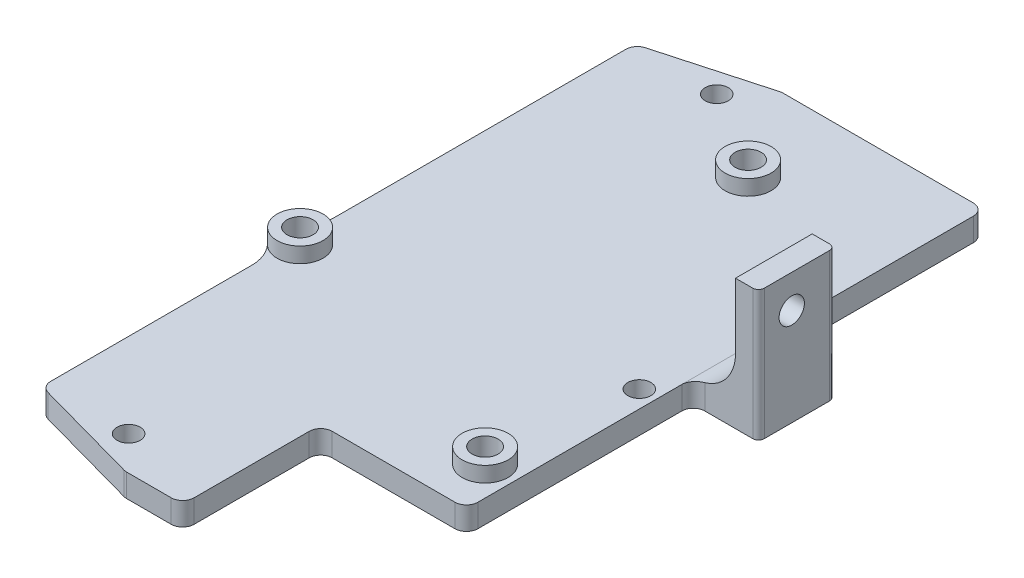
SolidWorks part; units mm, degrees
ref_plane "Front Plane" through (0, 0, 0) normal (0, 0, 1) x (1, 0, 0)
ref_plane "Top Plane" through (0, 0, 0) normal (0, 1, 0) x (1, 0, 0)
ref_plane "Right Plane" through (0, 0, 0) normal (1, 0, 0) x (0, 0, -1)
sketch "Sketch1" plane through (0, 0, 0) normal (0, 1, 0) x (1, 0, 0)
  line L0 (0, 0) -> (7, 0)
  line L1 (0, 3.75) -> (7, 3.75)
  line L2 (0, -3.75) -> (7, -3.75)
  circle A0 centre (0, 0) radius 3.75
  circle A1 centre (7, 0) radius 3.75
  dimension "D1" = 7.5
  dimension "D2" = 7
extrude "Boss-Extrude2" add sketch "Sketch1" along normal blind 30
sketch "Sketch4" plane through (0, 30, 0) normal (0, 1, 0) x (1, 0, 0)
  line L2 (7, 3.75) -> (0, 3.75)
  line L3 (0, -3.75) -> (7, -3.75)
  line L4 (7, 3.75) -> (0, 3.75)
  line L5 (0, -3.75) -> (7, -3.75)
  circle A0 centre (7, 0) radius 3.75
  arc A3 (0, 3.75) -> (0, -3.75) centre (0, 0) ccw
  arc A4 (7, -3.75) -> (7, 3.75) centre (7, 0) ccw
  arc A5 (0, 3.75) -> (0, -3.75) centre (0, 0) ccw
  arc A6 (7, -3.75) -> (7, 3.75) centre (7, 0) ccw
  line M6 (7, 3.75) -> (0, 3.75)
  arc M7 (0, 3.75) -> (0, -3.75) centre (0, 0) ccw
  line M8 (0, -3.75) -> (7, -3.75)
  dimension "D1" = 0
extrude "Cut-Extrude3" cut sketch "Sketch4" against normal blind 13 contours A0 M6 M7 M8
sketch "Sketch5" plane through (0, 0, 0) normal (0, -1, 0) x (1, 0, 0)
  line L0 (10.75, 0) -> (10.75, -52.5)
  line L1 (10.75, -52.5) -> (-39.25, -38.6338)
  line L2 (-39.25, -38.6338) -> (-39.25, -35)
  line L3 (-39.25, -35) -> (-9.25, -35)
  line L4 (-9.25, -35) -> (-9.25, 35)
  line L5 (-9.25, 35) -> (-39.25, 35)
  line L6 (-39.25, 35) -> (-39.25, 38.6338)
  line L7 (-39.25, 38.6338) -> (10.75, 52.5)
  line L8 (10.75, 52.5) -> (10.75, 0)
  arc A0 (7, -3.75) -> (7, 3.75) centre (7, 0) ccw construction
  dimension "D1" = 50
  dimension "D2" = 105
  dimension "D3" = 74.5
  dimension "D4" = 70
  dimension "D5" = 30
extrude "Boss-Extrude3" add sketch "Sketch5" against normal blind 3
sketch "Sketch6" plane through (0, 3, 0) normal (0, 1, 0) x (1, 0, 0)
  line L46 (-24.25, -42.7936) -> (-24.25, 42.7936)
  line L54 (10.75, 52.5) -> (-39.25, 38.6338)
  line L55 (10.75, -52.5) -> (10.75, 52.5)
  line L56 (-39.25, -38.6338) -> (10.75, -52.5)
  line L57 (-39.25, -35) -> (-39.25, -38.6338)
  line L58 (-9.25, -35) -> (-39.25, -35)
  line L59 (-9.25, 35) -> (-9.25, -35)
  line L60 (-39.25, 35) -> (-9.25, 35)
  line L61 (-39.25, 38.6338) -> (-39.25, 35)
  line L62 (10.75, 52.5) -> (-39.25, 38.6338)
  line L63 (10.75, -52.5) -> (10.75, 52.5)
  line L64 (-39.25, -38.6338) -> (10.75, -52.5)
  line L65 (-39.25, -35) -> (-39.25, -38.6338)
  line L66 (-9.25, -35) -> (-39.25, -35)
  line L67 (-9.25, 35) -> (-9.25, -35)
  line L68 (-39.25, 35) -> (-9.25, 35)
  line L69 (-39.25, 38.6338) -> (-39.25, 35)
  line M12 (10.75, 52.5) -> (-39.25, 38.6338)
  line M13 (-39.25, 38.6338) -> (-39.25, 35)
  line M14 (-39.25, 35) -> (-9.25, 35)
  line M16 (-9.25, -35) -> (-39.25, -35)
  line M17 (-39.25, -35) -> (-39.25, -38.6338)
  line M18 (-39.25, -38.6338) -> (10.75, -52.5)
  dimension "D2" = 15
  dimension "D1" = 0
extrude "Boss-Extrude4" add sketch "Sketch6" along normal blind 14 contours L46 M18 M16 M17 | L46 M14 M12 M13
sketch "Sketch7" plane through (0, 17, 0) normal (0, 1, 0) x (1, 0, 0)
  line L0 (-39.25, 38.6338) -> (-39.25, -38.6338)
  line L1 (-39.25, -38.6338) -> (-24.25, -42.7936)
  line L2 (-24.25, -42.7936) -> (2.25, -42.7936)
  line L3 (2.25, -42.7936) -> (2.25, 42.7936)
  line L4 (2.25, 42.7936) -> (-24.25, 42.7936)
  line L5 (-24.25, 42.7936) -> (-39.25, 38.6338)
  dimension "D1" = 41.5
extrude "Boss-Extrude5" add sketch "Sketch7" along normal blind 3
sketch "Sketch8" plane through (0, 20, 0) normal (0, 1, 0) x (1, 0, 0)
  line L0 (-28.25, 38.3422) -> (-28.25, 35)
  line L3 (-24.25, -42.7936) -> (-24.25, 42.7936)
  line L4 (-28.25, 38.3422) -> (-28.25, 41.6843)
  line L5 (-28.25, -41.6843) -> (-28.25, -38.3422)
  line L6 (-28.25, -38.3422) -> (-28.25, -35)
  line L11 (10.75, 52.5) -> (-39.25, 38.6338)
  line L12 (10.75, -52.5) -> (10.75, 52.5)
  line L13 (-39.25, -38.6338) -> (10.75, -52.5)
  line L14 (-39.25, -35) -> (-39.25, -38.6338)
  line L15 (-9.25, -35) -> (-39.25, -35)
  line L16 (-9.25, 35) -> (-9.25, -35)
  line L17 (-39.25, 35) -> (-9.25, 35)
  line L18 (-39.25, 38.6338) -> (-39.25, 35)
  line L19 (10.75, 52.5) -> (-39.25, 38.6338)
  line L20 (10.75, -52.5) -> (10.75, 52.5)
  line L21 (-39.25, -38.6338) -> (10.75, -52.5)
  line L22 (-39.25, -35) -> (-39.25, -38.6338)
  line L23 (-9.25, -35) -> (-39.25, -35)
  line L24 (-9.25, 35) -> (-9.25, -35)
  line L25 (-39.25, 35) -> (-9.25, 35)
  line L26 (-39.25, 38.6338) -> (-39.25, 35)
  circle A0 centre (-28.25, -38.3422) radius 1.5
  circle A1 centre (-28.25, 38.3422) radius 1.5
  dimension "D1" = 3
  dimension "D3" = 4
  dimension "D2" = 0
extrude "Cut-Extrude4" cut sketch "Sketch8" against normal through all contours A1 | A0
sketch "Sketch3" plane through (0, 0, 0) normal (0, -1, 0) x (1, 0, 0)
  circle A0 centre (0, 0) radius 1.5
  dimension "D1" = 3
extrude "Cut-Extrude2" cut sketch "Sketch3" against normal through all
sketch "Sketch2" plane through (0, 30, 0) normal (0, 1, 0) x (1, 0, 0)
  circle A0 centre (7, 0) radius 1.5
  dimension "D1" = 3
extrude "Cut-Extrude1" cut sketch "Sketch2" against normal blind 30
sketch "Sketch9" plane through (2.25, 0, 0) normal (1, 0, 0) x (0, 0, -1)
  line L0 (3.75, 17) -> (42.7936, 17) construction
  line L1 (4.7936, 34) -> (14.7936, 34)
  line L2 (4.7936, 34) -> (4.7936, 17)
  line L3 (4.7936, 17) -> (14.7936, 17)
  line L4 (14.7936, 34) -> (14.7936, 17)
  line L6 (42.7936, 20) -> (42.7936, 17) construction
  dimension "D1" = 28
  dimension "D2" = 10
  dimension "D3" = 17
extrude "Boss-Extrude6" add sketch "Sketch9" along normal blind 8.5
sketch "Sketch11" plane through (10.75, 0, 0) normal (1, 0, 0) x (0, 0, -1)
  line L0 (43.5, 3) -> (43.5, 4)
  line L1 (51.5, 4) -> (51.5, 3)
  line L5 (-52.5, 0) -> (52.5, 0)
  line L6 (52.5, 0) -> (52.5, 3)
  line L7 (52.5, 3) -> (0, 3)
  line L8 (0, 3) -> (-52.5, 3)
  line L9 (-52.5, 3) -> (-52.5, 0)
  line L10 (-52.5, 0) -> (52.5, 0)
  line L11 (52.5, 0) -> (52.5, 3)
  line L12 (52.5, 3) -> (0, 3)
  line L13 (0, 3) -> (-52.5, 3)
  line L14 (-52.5, 3) -> (-52.5, 0)
  arc A0 (43.5, 4) -> (51.5, 4) centre (47.5, 4) cw
  circle A1 centre (47.5, 4) radius 0.875
  line M8 (52.5, 3) -> (0, 3)
  dimension "D4" = 4
  dimension "D5" = 1.75
  dimension "D2" = 1
  dimension "D3" = 5
  dimension "D1" = 0
extrude "Boss-Extrude7" add sketch "Sketch11" against normal blind 10 contours A0 L0 L1 A1 M8
sketch "Sketch12" plane through (0, 3, 0) normal (0, -1, 0) x (1, 0, 0)
  line L3 (7.1441, -51.5) -> (0.75, -49.7268)
  line L4 (0.75, -49.7268) -> (0.75, -51.5)
  line L5 (0.75, -51.5) -> (7.1441, -51.5)
  line L6 (7.1441, -51.5) -> (0.75, -49.7268)
  line L7 (0.75, -49.7268) -> (0.75, -51.5)
  line L8 (0.75, -51.5) -> (7.1441, -51.5)
  dimension "D1" = 0
extrude "Cut-Extrude6" cut sketch "Sketch12" against normal blind 10
sketch "Sketch13" plane through (0, 0, -14.7936) normal (0, 0, -1) x (-1, 0, 0)
  line L0 (-7.75, 34) -> (-7.75, 25.5)
  line L1 (-2.25, 20) -> (1.5008, 20)
  line L5 (-2.25, 17) -> (-2.25, 20)
  line L6 (-2.25, 20) -> (-2.25, 34)
  line L7 (-2.25, 34) -> (-10.75, 34)
  line L8 (-10.75, 34) -> (-10.75, 17)
  line L9 (-10.75, 17) -> (-2.25, 17)
  line L10 (-2.25, 17) -> (-2.25, 20)
  line L11 (-2.25, 20) -> (-2.25, 34)
  line L12 (-2.25, 34) -> (-10.75, 34)
  line L13 (-10.75, 34) -> (-10.75, 17)
  line L14 (-10.75, 17) -> (-2.25, 17)
  arc A0 (-7.75, 25.5) -> (-2.25, 20) centre (-2.25, 25.5) ccw
  line M7 (-2.25, 20) -> (-2.25, 34)
  line M8 (-2.25, 34) -> (-10.75, 34)
  dimension "D2" = 3
  dimension "D1" = 0
extrude "Cut-Extrude7" cut sketch "Sketch13" against normal up to next contours L0 A0 M7 M8
sketch "Sketch14" plane through (10.75, 0, 0) normal (1, 0, 0) x (0, 0, -1)
  line L0 (14.7936, 34) -> (4.7936, 34) construction
  line L1 (4.7936, 34) -> (4.7936, 17) construction
  circle A0 centre (9.1236, 29.69) radius 1.65
  dimension "D3" = 3.3
  dimension "D1" = 4.31
  dimension "D2" = 4.33
extrude "Cut-Extrude8" cut sketch "Sketch14" against normal blind 10 contours A0
sketch "Sketch15" plane through (0, 20, 0) normal (0, 1, 0) x (1, 0, 0)
  line L0 (-39.25, -25.7936) -> (-17.25, -25.7936)
  line L1 (-39.25, 38.6338) -> (-39.25, -38.6338) construction
  line L2 (-17.25, -25.7936) -> (-17.25, -42.7936)
  line L4 (-24.25, -42.7936) -> (2.25, -42.7936) construction
  line L13 (-24.25, 42.7936) -> (-39.25, 38.6338)
  line L14 (-39.25, 38.6338) -> (-39.25, -38.6338)
  line L15 (-39.25, -38.6338) -> (-24.25, -42.7936)
  line L16 (-24.25, -42.7936) -> (2.25, -42.7936)
  line L17 (2.25, -42.7936) -> (2.25, 4.7936)
  line L18 (2.25, 4.7936) -> (2.25, 14.7936)
  line L19 (2.25, 14.7936) -> (2.25, 42.7936)
  line L20 (2.25, 42.7936) -> (-24.25, 42.7936)
  line L21 (-24.25, 42.7936) -> (-39.25, 38.6338)
  line L22 (-39.25, 38.6338) -> (-39.25, -38.6338)
  line L23 (-39.25, -38.6338) -> (-24.25, -42.7936)
  line L24 (-24.25, -42.7936) -> (2.25, -42.7936)
  line L25 (2.25, -42.7936) -> (2.25, 4.7936)
  line L26 (2.25, 4.7936) -> (2.25, 14.7936)
  line L27 (2.25, 14.7936) -> (2.25, 42.7936)
  line L28 (2.25, 42.7936) -> (-24.25, 42.7936)
  circle M12 centre (-28.25, -38.3422) radius 1.5
  line M15 (-39.25, 38.6338) -> (-39.25, -38.6338)
  line M16 (-39.25, -38.6338) -> (-24.25, -42.7936)
  line M17 (-24.25, -42.7936) -> (2.25, -42.7936)
  dimension "D1" = 22
  dimension "D2" = 17
  dimension "D3" = 0
extrude "Boss-Extrude8" add sketch "Sketch15" along normal blind 20 contours L2 L0 M15 M16 M17 M12
sketch "Sketch16" plane through (-17.25, 0, 0) normal (1, 0, 0) x (0, 0, -1)
  line L0 (-25.7936, 40) -> (-25.7936, 20) construction
  line L1 (-42.7936, 40) -> (-25.7936, 40)
  line L2 (-42.7936, 40) -> (-42.7936, 35)
  line L3 (-42.7936, 35) -> (-25.7936, 35)
  line L4 (-25.7936, 40) -> (-25.7936, 35)
  dimension "D1" = 5
extrude "Boss-Extrude9" add sketch "Sketch16" along normal blind 25
sketch "Sketch17" plane through (0, 40, 0) normal (0, 1, 0) x (1, 0, 0)
  line L0 (-0.25, -34.2936) -> (7.75, -34.2936)
  line L1 (7.75, -25.7936) -> (7.75, -42.7936) construction
  circle A0 centre (-0.25, -34.2936) radius 6.25
  dimension "D1" = 12.5
  dimension "D2" = 8
extrude "Cut-Extrude9" cut sketch "Sketch17" against normal up to next contours A0
sketch "Sketch18" plane through (0, 40, 0) normal (0, 1, 0) x (1, 0, 0)
  circle A0 centre (-0.25, -34.2936) radius 11.6726
  circle A1 centre (-0.25, -34.2936) radius 6.25 construction
  circle A2 centre (-0.25, -34.2936) radius 6.25
extrude "Boss-Extrude10" add sketch "Sketch18" against normal up to surface (5 mm away) up to face at (-0.25, 35, 40.5436)
fillet "Fillet1" radius 3 1 edges at (-17.25, 35, 34.2936)
sketch "Sketch19" plane through (0, 20, 0) normal (0, 1, 0) x (1, 0, 0)
  line L1 (2.25, -42.7936) -> (-16.75, -42.7936)
  line L2 (2.25, -42.7936) -> (2.25, -24.7936)
  line L3 (2.25, -24.7936) -> (-16.75, -24.7936)
  line L4 (-16.75, -42.7936) -> (-16.75, -24.7936)
  dimension "D1" = 19
  dimension "D2" = 18
extrude "Cut-Extrude10" cut sketch "Sketch19" against normal up to next
fillet "Fillet2" radius 3 8 edges at (9.6517, 3, 2.6517) (9.6517, 3, -2.6517) (3.5, 3, -3.75) (-3.75, 3, 0) (-24.25, 3, -38.8968) (5.75, 3, -43.5) (-24.25, 3, 38.8968) (3.5, 3, 3.75)
fillet "Fillet3" radius 1.5 8 edges at (2.25, 18.5, 24.7936) (-16.75, 18.5, 24.7936) (-8.25, 37.5, 25.7936) (-39.25, 30, 25.7936) (-39.25, 20, 38.6338) (-39.25, 10, -38.6338)
sketch "Sketch22" plane through (0, 0, -42.7936) normal (0, 0, -1) x (-1, 0, 0)
  line L0 (-2.25, 20) -> (-2.25, 38.7401)
  line L1 (-2.25, 38.7401) -> (-18.9437, 38.7401)
  line L2 (-18.9437, 38.7401) -> (-18.9437, 17)
  line L3 (-18.9437, 17) -> (-2.25, 17)
  line L4 (-2.25, 17) -> (24.25, 17)
  line L5 (24.25, 17) -> (24.25, 20)
  line L6 (24.25, 20) -> (-2.25, 20)
  line L7 (-2.25, 20) -> (-2.25, 17)
  line L8 (-2.25, 17) -> (24.25, 17)
  line L9 (24.25, 17) -> (24.25, 20)
  line L10 (24.25, 20) -> (-2.25, 20)
  line L11 (-2.25, 20) -> (-2.25, 17)
  line L12 (24.25, 20) -> (43.5657, 20)
  line L13 (43.5657, 20) -> (43.5657, 17)
  line L14 (43.5657, 17) -> (24.25, 17)
  line L16 (-30.6104, 54.8459) -> (63.2121, 54.8459)
  line L17 (-30.6104, 54.8459) -> (-30.6104, -17.9434)
  line L18 (-30.6104, -17.9434) -> (63.2121, -17.9434)
  line L19 (63.2121, 54.8459) -> (63.2121, -17.9434)
  line M5 (-2.25, 17) -> (24.25, 17)
  line M7 (24.25, 20) -> (-2.25, 20)
  dimension "D1" = 0
extrude "Cut-Extrude12" cut sketch "Sketch22" against normal through all contours L19 L16 L17 L18 L13 L14 L3 L2 L1 L0 L12 M5 M7
fillet "Fillet4" radius 1.5 6 edges at (2.25, 18.5, -14.7936) (2.25, 18.5, -4.7936) (-24.25, 18.5, -42.7936) (2.25, 18.5, -42.7936) (-24.25, 18.5, 42.7936) (-16.75, 18.5, 42.7936)
fillet "Fillet6" radius 0.75 2 edges at (10.75, 25.5, -4.7936) (10.75, 25.5, -14.7936)
sketch "Sketch23" plane through (0, 20, 0) normal (0, 1, 0) x (1, 0, 0)
  circle A0 centre (-16.8, 30.9836) radius 1.7 construction
  circle A1 centre (-1.56, -18.5464) radius 1.7 construction
  circle A2 centre (-38.39, -5.8464) radius 1.7 construction
  circle A3 centre (-16.8, 30.9836) radius 1.7
  circle A4 centre (-1.56, -18.5464) radius 1.7
  circle A5 centre (-38.39, -5.8464) radius 1.7
  line M5 (-39.25, 37.4931) -> (-39.25, -37.4931)
extrude "Cut-Extrude13" cut sketch "Sketch23" against normal blind 10 contours A5 M5 | A3 | A4
sketch "Sketch24" plane through (0, 20, 0) normal (0, 1, 0) x (1, 0, 0)
  line L11 (-39.25, -7.3128) -> (-39.25, -37.4931)
  line L12 (-38.1509, -38.9386) -> (-24.4467, -42.7391)
  line L13 (-24.0459, -42.7936) -> (-18.25, -42.7936)
  line L14 (-16.75, -41.2936) -> (-16.75, -26.2936)
  line L15 (-15.25, -24.7936) -> (0.75, -24.7936)
  line L16 (2.25, -23.2936) -> (2.25, 3.2936)
  line L17 (2.25, 3.2936) -> (2.25, 16.2936)
  line L18 (2.25, 16.2936) -> (2.25, 41.2936)
  line L19 (0.75, 42.7936) -> (-24.0459, 42.7936)
  line L20 (-24.4467, 42.7391) -> (-38.1509, 38.9386)
  line L21 (-39.25, 37.4931) -> (-39.25, -4.3799)
  line L22 (-39.25, -7.3128) -> (-39.25, -37.4931)
  line L23 (-38.1509, -38.9386) -> (-24.4467, -42.7391)
  line L24 (-24.0459, -42.7936) -> (-18.25, -42.7936)
  line L25 (-16.75, -41.2936) -> (-16.75, -26.2936)
  line L26 (-15.25, -24.7936) -> (0.75, -24.7936)
  line L27 (2.25, -23.2936) -> (2.25, 3.2936)
  line L28 (2.25, 3.2936) -> (2.25, 16.2936)
  line L29 (2.25, 16.2936) -> (2.25, 41.2936)
  line L30 (0.75, 42.7936) -> (-24.0459, 42.7936)
  line L31 (-24.4467, 42.7391) -> (-38.1509, 38.9386)
  line L32 (-39.25, 37.4931) -> (-39.25, -4.3799)
  circle A0 centre (-38.39, -5.8464) radius 3
  circle A1 centre (-38.39, -5.8464) radius 1.7
  arc A9 (-39.25, -7.3128) -> (-39.25, -4.3799) centre (-38.39, -5.8464) ccw
  arc A10 (-39.25, -37.4931) -> (-38.1509, -38.9386) centre (-37.75, -37.4931) ccw
  arc A11 (-24.4467, -42.7391) -> (-24.0459, -42.7936) centre (-24.0459, -41.2936) ccw
  arc A12 (-18.25, -42.7936) -> (-16.75, -41.2936) centre (-18.25, -41.2936) ccw
  arc A13 (-15.25, -24.7936) -> (-16.75, -26.2936) centre (-15.25, -26.2936) ccw
  arc A14 (0.75, -24.7936) -> (2.25, -23.2936) centre (0.75, -23.2936) ccw
  arc A15 (2.25, 41.2936) -> (0.75, 42.7936) centre (0.75, 41.2936) ccw
  arc A16 (-24.0459, 42.7936) -> (-24.4467, 42.7391) centre (-24.0459, 41.2936) ccw
  arc A17 (-38.1509, 38.9386) -> (-39.25, 37.4931) centre (-37.75, 37.4931) ccw
  arc A18 (-39.25, -7.3128) -> (-39.25, -4.3799) centre (-38.39, -5.8464) ccw
  arc A19 (-39.25, -37.4931) -> (-38.1509, -38.9386) centre (-37.75, -37.4931) ccw
  arc A20 (-24.4467, -42.7391) -> (-24.0459, -42.7936) centre (-24.0459, -41.2936) ccw
  arc A21 (-18.25, -42.7936) -> (-16.75, -41.2936) centre (-18.25, -41.2936) ccw
  arc A22 (-15.25, -24.7936) -> (-16.75, -26.2936) centre (-15.25, -26.2936) ccw
  arc A23 (0.75, -24.7936) -> (2.25, -23.2936) centre (0.75, -23.2936) ccw
  arc A24 (2.25, 41.2936) -> (0.75, 42.7936) centre (0.75, 41.2936) ccw
  arc A25 (-24.0459, 42.7936) -> (-24.4467, 42.7391) centre (-24.0459, 41.2936) ccw
  arc A26 (-38.1509, 38.9386) -> (-39.25, 37.4931) centre (-37.75, 37.4931) ccw
  line M24 (-39.25, -7.3128) -> (-39.25, -37.4931)
  dimension "D2" = 6
  dimension "D1" = 0
extrude "Boss-Extrude11" add sketch "Sketch24" against normal up to surface (3 mm away) contours A1 L32 A0 M24 up to face at (-1.56, 17, 20.2464)
fillet "Fillet7" radius 5 1 edges at (-39.25, 18.5, 2.9723)
sketch "Sketch25" plane through (0, 20, 0) normal (0, 1, 0) x (1, 0, 0)
  line L11 (-39.25, 37.4931) -> (-39.25, -0.4002)
  line L12 (-39.25, -11.2925) -> (-39.25, -37.4931)
  line L13 (-38.1509, -38.9386) -> (-24.4467, -42.7391)
  line L14 (-24.0459, -42.7936) -> (-18.25, -42.7936)
  line L15 (-16.75, -41.2936) -> (-16.75, -26.2936)
  line L16 (-15.25, -24.7936) -> (0.75, -24.7936)
  line L17 (2.25, -23.2936) -> (2.25, 3.2936)
  line L18 (2.25, 3.2936) -> (2.25, 16.2936)
  line L19 (2.25, 16.2936) -> (2.25, 41.2936)
  line L20 (0.75, 42.7936) -> (-24.0459, 42.7936)
  line L21 (-24.4467, 42.7391) -> (-38.1509, 38.9386)
  line L22 (-39.25, 37.4931) -> (-39.25, -0.4002)
  line L23 (-39.25, -11.2925) -> (-39.25, -37.4931)
  line L24 (-38.1509, -38.9386) -> (-24.4467, -42.7391)
  line L25 (-24.0459, -42.7936) -> (-18.25, -42.7936)
  line L26 (-16.75, -41.2936) -> (-16.75, -26.2936)
  line L27 (-15.25, -24.7936) -> (0.75, -24.7936)
  line L28 (2.25, -23.2936) -> (2.25, 3.2936)
  line L29 (2.25, 3.2936) -> (2.25, 16.2936)
  line L30 (2.25, 16.2936) -> (2.25, 41.2936)
  line L31 (0.75, 42.7936) -> (-24.0459, 42.7936)
  line L32 (-24.4467, 42.7391) -> (-38.1509, 38.9386)
  circle A0 centre (-38.39, -5.8464) radius 3
  circle A1 centre (-1.56, -18.5464) radius 3
  circle A2 centre (-16.8, 30.9836) radius 3
  arc A11 (-40.5875, -3.8041) -> (-39.25, -0.4002) centre (-44.25, -0.4002) ccw
  arc A12 (-40.5875, -3.8041) -> (-40.5875, -7.8887) centre (-38.39, -5.8464) ccw
  arc A13 (-39.25, -11.2925) -> (-40.5875, -7.8887) centre (-44.25, -11.2925) ccw
  arc A14 (-39.25, -37.4931) -> (-38.1509, -38.9386) centre (-37.75, -37.4931) ccw
  arc A15 (-24.4467, -42.7391) -> (-24.0459, -42.7936) centre (-24.0459, -41.2936) ccw
  arc A16 (-18.25, -42.7936) -> (-16.75, -41.2936) centre (-18.25, -41.2936) ccw
  arc A17 (-15.25, -24.7936) -> (-16.75, -26.2936) centre (-15.25, -26.2936) ccw
  arc A18 (0.75, -24.7936) -> (2.25, -23.2936) centre (0.75, -23.2936) ccw
  arc A19 (2.25, 41.2936) -> (0.75, 42.7936) centre (0.75, 41.2936) ccw
  arc A20 (-24.0459, 42.7936) -> (-24.4467, 42.7391) centre (-24.0459, 41.2936) ccw
  arc A21 (-38.1509, 38.9386) -> (-39.25, 37.4931) centre (-37.75, 37.4931) ccw
  arc A22 (-40.5875, -3.8041) -> (-39.25, -0.4002) centre (-44.25, -0.4002) ccw
  arc A23 (-40.5875, -3.8041) -> (-40.5875, -7.8887) centre (-38.39, -5.8464) ccw
  arc A24 (-39.25, -11.2925) -> (-40.5875, -7.8887) centre (-44.25, -11.2925) ccw
  arc A25 (-39.25, -37.4931) -> (-38.1509, -38.9386) centre (-37.75, -37.4931) ccw
  arc A26 (-24.4467, -42.7391) -> (-24.0459, -42.7936) centre (-24.0459, -41.2936) ccw
  arc A27 (-18.25, -42.7936) -> (-16.75, -41.2936) centre (-18.25, -41.2936) ccw
  arc A28 (-15.25, -24.7936) -> (-16.75, -26.2936) centre (-15.25, -26.2936) ccw
  arc A29 (0.75, -24.7936) -> (2.25, -23.2936) centre (0.75, -23.2936) ccw
  arc A30 (2.25, 41.2936) -> (0.75, 42.7936) centre (0.75, 41.2936) ccw
  arc A31 (-24.0459, 42.7936) -> (-24.4467, 42.7391) centre (-24.0459, 41.2936) ccw
  arc A32 (-38.1509, 38.9386) -> (-39.25, 37.4931) centre (-37.75, 37.4931) ccw
  arc M25 (-40.5875, -3.8041) -> (-40.5875, -7.8887) centre (-38.39, -5.8464) ccw
  circle M45 centre (-1.56, -18.5464) radius 1.7
  circle M46 centre (-16.8, 30.9836) radius 1.7
  circle M47 centre (-38.39, -5.8464) radius 1.7
  dimension "D2" = 6
  dimension "D3" = 6
  dimension "D4" = 6
  dimension "D1" = 0
extrude "Boss-Extrude12" add sketch "Sketch25" along normal blind 2 contours A1 M45 | A0 M25 M47 | A2 M46
